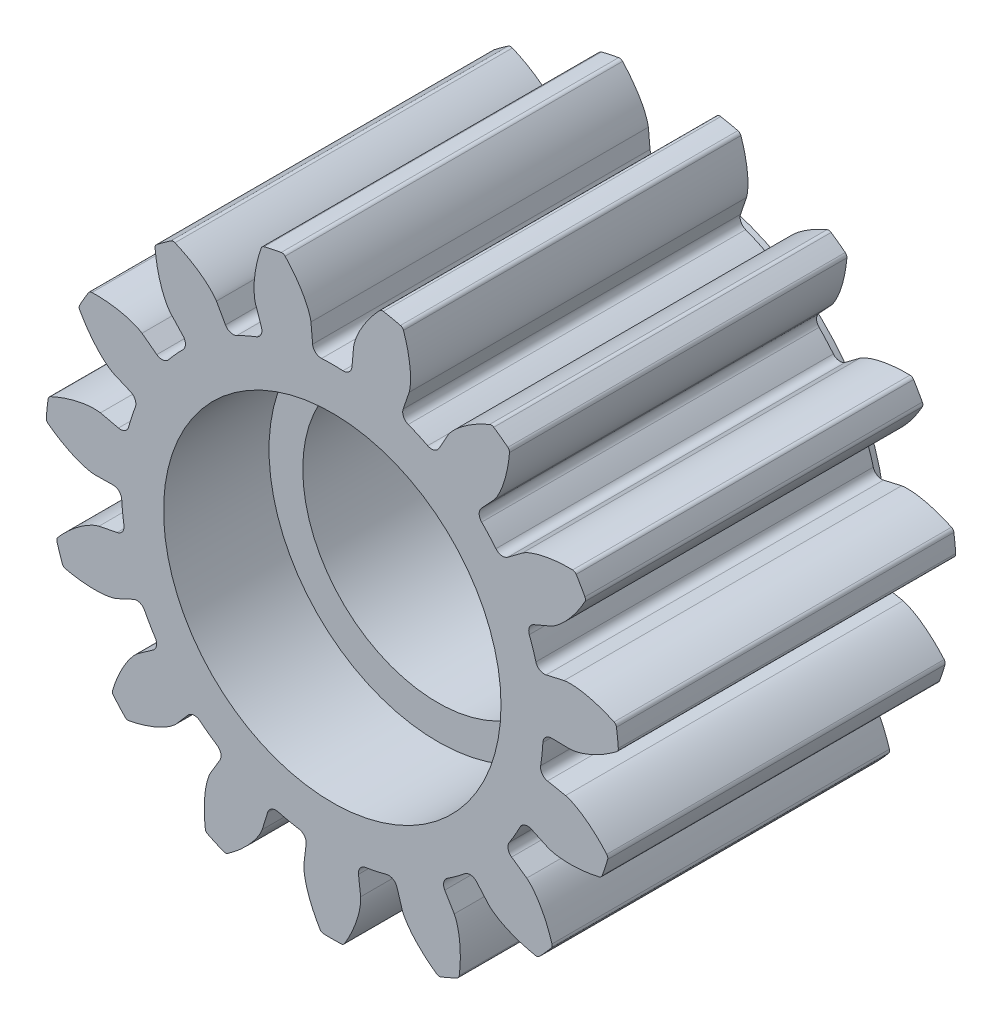
SolidWorks part; units mm, degrees
material "Alloy Steel"
ref_plane "Front" through (0, 0, 0) normal (0, 0, 1) x (1, 0, 0)
ref_plane "Top" through (0, 0, 0) normal (0, 1, 0) x (1, 0, 0)
ref_plane "Right" through (0, 0, 0) normal (1, 0, 0) x (0, 0, -1)
sketch "Sketch1" plane through (0, 0, 0) normal (0, 0, 1) x (1, 0, 0)
  circle A0 centre (0, 0) radius 10.795
  dimension "OutsideDiameter" = 21.59
extrude "Boss-Extrude1" add sketch "Sketch1" along normal blind 12.7
sketch "Sketch3" plane through (0, 0, 0) normal (0, 0, 1) x (1, 0, 0)
  line L0 (0, 0) -> (43.7181, 0) construction
  line L2 (0, 0) -> (-0.712, 7.9055) construction
  line L3 (0, 0) -> (0.712, 7.9055) construction
  line L4 (0.712, 7.9055) -> (0.8028, 8.9145) construction
  line L5 (0, 0) -> (0, 61.276) construction
  line L6 (-0.712, 7.9055) -> (-0.8028, 8.9145) construction
  circle A0 centre (0, 0) radius 10.795 construction
  circle A1 centre (0, 0) radius 9.525 construction
  circle A2 centre (0, 0) radius 8.9506 construction
  arc A3 (0.712, 7.9055) -> (-0.712, 7.9055) centre (0, 0) ccw construction
  arc A5 (1.8351, 10.6379) -> (-1.8351, 10.6379) centre (0, 0) ccw
  spline S0 degree 4 poles (-0.8028, 8.9145) (-0.8031, 8.9175) (-0.8041, 8.9259) (-0.8066, 8.9416) (-0.8113, 8.9673) (-0.8183, 8.9998) (-0.8287, 9.0417) (-0.8426, 9.0906) (-0.8594, 9.1441) (-0.8795, 9.2019) (-0.9011, 9.2592) (-0.9242, 9.316) (-0.9484, 9.3722) (-0.9793, 9.4398) (-1.0185, 9.5203) (-1.0674, 9.6134) (-1.1265, 9.7178) (-1.1905, 9.8228) (-1.2566, 9.925) (-1.327, 10.0269) (-1.3976, 10.1244) (-1.4745, 10.2242) (-1.5473, 10.3155) (-1.6328, 10.416) (-1.7029, 10.4966) (-1.7995, 10.6009) (-1.8578, 10.6619) (-1.9274, 10.7325) (-1.9591, 10.7635) (-1.9785, 10.7826) knots 0 0 0 0 0 0.005377 0.015084 0.028532 0.04661 0.064855 0.092111 0.119476 0.146842 0.174209 0.201575 0.228941 0.256307 0.307035 0.361767 0.4165 0.471232 0.525964 0.580697 0.635429 0.690161 0.744894 0.799626 0.854358 0.909091 0.954545 1 1 1 1 1 construction
  spline S1 degree 4 poles (-0.8028, 8.9145) (-0.8031, 8.9175) (-0.8041, 8.9259) (-0.8066, 8.9416) (-0.8113, 8.9673) (-0.8183, 8.9998) (-0.8287, 9.0417) (-0.8426, 9.0906) (-0.8594, 9.1441) (-0.8795, 9.2019) (-0.9011, 9.2592) (-0.9242, 9.316) (-0.9484, 9.3722) (-0.9793, 9.4398) (-1.0185, 9.5203) (-1.0674, 9.6134) (-1.1265, 9.7178) (-1.1905, 9.8228) (-1.2566, 9.925) (-1.327, 10.0269) (-1.3976, 10.1244) (-1.4745, 10.2242) (-1.5473, 10.3155) (-1.6328, 10.416) (-1.7029, 10.4966) (-1.7786, 10.5782) (-1.8159, 10.6178) (-1.8351, 10.6379) knots 0 0 0 0 0 0.005377 0.015084 0.028532 0.04661 0.064855 0.092111 0.119476 0.146842 0.174209 0.201575 0.228941 0.256307 0.307035 0.361767 0.4165 0.471232 0.525964 0.580697 0.635429 0.690161 0.744894 0.799626 0.854358 0.909091 0.909091 0.909091 0.909091 0.909091
  spline S2 degree 4 poles (0.8028, 8.9145) (0.8031, 8.9175) (0.8041, 8.9259) (0.8066, 8.9416) (0.8113, 8.9673) (0.8183, 8.9998) (0.8287, 9.0417) (0.8426, 9.0906) (0.8594, 9.1441) (0.8795, 9.2019) (0.9011, 9.2592) (0.9242, 9.316) (0.9484, 9.3722) (0.9793, 9.4398) (1.0185, 9.5203) (1.0674, 9.6134) (1.1265, 9.7178) (1.1905, 9.8228) (1.2566, 9.925) (1.327, 10.0269) (1.3976, 10.1244) (1.4745, 10.2242) (1.5473, 10.3155) (1.6328, 10.416) (1.7029, 10.4966) (1.7995, 10.6009) (1.8578, 10.6619) (1.9274, 10.7325) (1.9591, 10.7635) (1.9785, 10.7826) knots 0 0 0 0 0 0.005377 0.015084 0.028532 0.04661 0.064855 0.092111 0.119476 0.146842 0.174209 0.201575 0.228941 0.256307 0.307035 0.361767 0.4165 0.471232 0.525964 0.580697 0.635429 0.690161 0.744894 0.799626 0.854358 0.909091 0.954545 1 1 1 1 1 construction
  spline S3 degree 4 poles (0.8028, 8.9145) (0.8031, 8.9175) (0.8041, 8.9259) (0.8066, 8.9416) (0.8113, 8.9673) (0.8183, 8.9998) (0.8287, 9.0417) (0.8426, 9.0906) (0.8594, 9.1441) (0.8795, 9.2019) (0.9011, 9.2592) (0.9242, 9.316) (0.9484, 9.3722) (0.9793, 9.4398) (1.0185, 9.5203) (1.0674, 9.6134) (1.1265, 9.7178) (1.1905, 9.8228) (1.2566, 9.925) (1.327, 10.0269) (1.3976, 10.1244) (1.4745, 10.2242) (1.5473, 10.3155) (1.6328, 10.416) (1.7029, 10.4966) (1.7786, 10.5782) (1.8159, 10.6178) (1.8351, 10.6379) knots 0 0 0 0 0 0.005377 0.015084 0.028532 0.04661 0.064855 0.092111 0.119476 0.146842 0.174209 0.201575 0.228941 0.256307 0.307035 0.361767 0.4165 0.471232 0.525964 0.580697 0.635429 0.690161 0.744894 0.799626 0.854358 0.909091 0.909091 0.909091 0.909091 0.909091
  dimension "OutsideDiameter" = 21.59
  dimension "PitchCircle" = 19.05
  dimension "BaseCircle" = 17.9011
  dimension "DedendumCircle" = 15.875
sketch "DCLTBC" plane through (0, 0, 0) normal (0, 0, 1) x (1, 0, 0)
  line L0 (0, 0) -> (41.04, 0) construction
  line L1 (-0.712, 7.9055) -> (-0.8028, 8.9145) construction
  line L2 (0.712, 7.9055) -> (0.8028, 8.9145) construction
  line L3 (-0.7404, 8.2217) -> (-0.8028, 8.9145)
  line L4 (0.7404, 8.2217) -> (0.8028, 8.9145)
  line L5 (0, 0) -> (0, 104.9356) construction
  circle A0 centre (0, 0) radius 10.795
  circle A1 centre (0, 0) radius 9.525 construction
  circle A2 centre (0, 0) radius 8.9506 construction
  arc A3 (0.712, 7.9055) -> (-0.712, 7.9055) centre (0, 0) ccw construction
  arc A4 (0.4015, 7.9273) -> (-0.4015, 7.9273) centre (0, 0) ccw
  arc A5 (-0.7404, 8.2217) -> (-0.4015, 7.9273) centre (-0.4179, 8.2508) ccw
  arc A7 (0.7404, 8.2217) -> (0.4015, 7.9273) centre (0.4179, 8.2508) cw
  spline S0 degree 4 poles (-995.1793, -96.8983) (-12.295, 6.8209) (-0.9092, 8.2064) (-0.7443, 8.6021) (-0.8113, 8.9673) (-0.8183, 8.9998) (-0.8287, 9.0417) (-0.8426, 9.0906) (-0.8594, 9.1441) (-0.8795, 9.2019) (-0.9011, 9.2592) (-0.9242, 9.316) (-0.9484, 9.3722) (-0.9793, 9.4398) (-1.0185, 9.5203) (-1.0674, 9.6134) (-1.1265, 9.7178) (-1.1905, 9.8228) (-1.2566, 9.925) (-1.327, 10.0269) (-1.3976, 10.1244) (-1.4745, 10.2242) (-1.5473, 10.3155) (-1.6328, 10.416) (-2.006, 10.8448) (-3.4164, 12.2251) (15.2695, -7.4447) (-693.9148, 732.4306) knots -0.616876 -0.616876 -0.616876 -0.616876 -0.616876 0.005377 0.015084 0.028532 0.04661 0.064855 0.092111 0.119476 0.146842 0.174209 0.201575 0.228941 0.256307 0.307035 0.361767 0.4165 0.471232 0.525964 0.580697 0.635429 0.690161 0.744894 0.799626 0.854358 1.855242 1.855242 1.855242 1.855242 1.855242 only from (-0.8028, 8.9145) to (-1.8351, 10.6379) construction
  spline S1 degree 4 poles (995.1793, -96.8983) (12.295, 6.8209) (0.9092, 8.2064) (0.7443, 8.6021) (0.8113, 8.9673) (0.8183, 8.9998) (0.8287, 9.0417) (0.8426, 9.0906) (0.8594, 9.1441) (0.8795, 9.2019) (0.9011, 9.2592) (0.9242, 9.316) (0.9484, 9.3722) (0.9793, 9.4398) (1.0185, 9.5203) (1.0674, 9.6134) (1.1265, 9.7178) (1.1905, 9.8228) (1.2566, 9.925) (1.327, 10.0269) (1.3976, 10.1244) (1.4745, 10.2242) (1.5473, 10.3155) (1.6328, 10.416) (2.006, 10.8448) (3.4164, 12.2251) (-15.2695, -7.4447) (693.9148, 732.4306) knots -0.616876 -0.616876 -0.616876 -0.616876 -0.616876 0.005377 0.015084 0.028532 0.04661 0.064855 0.092111 0.119476 0.146842 0.174209 0.201575 0.228941 0.256307 0.307035 0.361767 0.4165 0.471232 0.525964 0.580697 0.635429 0.690161 0.744894 0.799626 0.854358 1.855242 1.855242 1.855242 1.855242 1.855242 only from (0.8028, 8.9145) to (1.8351, 10.6379) construction
  spline S2 degree 4 poles (-0.8028, 8.9145) (-0.8031, 8.9175) (-0.8041, 8.9259) (-0.8066, 8.9416) (-0.8113, 8.9673) (-0.8183, 8.9998) (-0.8287, 9.0417) (-0.8426, 9.0906) (-0.8594, 9.1441) (-0.8795, 9.2019) (-0.9011, 9.2592) (-0.9242, 9.316) (-0.9484, 9.3722) (-0.9793, 9.4398) (-1.0185, 9.5203) (-1.0674, 9.6134) (-1.1265, 9.7178) (-1.1905, 9.8228) (-1.2566, 9.925) (-1.327, 10.0269) (-1.3976, 10.1244) (-1.4745, 10.2242) (-1.5473, 10.3155) (-1.6328, 10.416) (-1.7029, 10.4966) (-1.7786, 10.5782) (-1.8159, 10.6178) (-1.8351, 10.6379) knots 0 0 0 0 0 0.005377 0.015084 0.028532 0.04661 0.064855 0.092111 0.119476 0.146842 0.174209 0.201575 0.228941 0.256307 0.307035 0.361767 0.4165 0.471232 0.525964 0.580697 0.635429 0.690161 0.744894 0.799626 0.854358 0.909091 0.909091 0.909091 0.909091 0.909091
  spline S3 degree 4 poles (0.8028, 8.9145) (0.8031, 8.9175) (0.8041, 8.9259) (0.8066, 8.9416) (0.8113, 8.9673) (0.8183, 8.9998) (0.8287, 9.0417) (0.8426, 9.0906) (0.8594, 9.1441) (0.8795, 9.2019) (0.9011, 9.2592) (0.9242, 9.316) (0.9484, 9.3722) (0.9793, 9.4398) (1.0185, 9.5203) (1.0674, 9.6134) (1.1265, 9.7178) (1.1905, 9.8228) (1.2566, 9.925) (1.327, 10.0269) (1.3976, 10.1244) (1.4745, 10.2242) (1.5473, 10.3155) (1.6328, 10.416) (1.7029, 10.4966) (1.7786, 10.5782) (1.8159, 10.6178) (1.8351, 10.6379) knots 0 0 0 0 0 0.005377 0.015084 0.028532 0.04661 0.064855 0.092111 0.119476 0.146842 0.174209 0.201575 0.228941 0.256307 0.307035 0.361767 0.4165 0.471232 0.525964 0.580697 0.635429 0.690161 0.744894 0.799626 0.854358 0.909091 0.909091 0.909091 0.909091 0.909091
  dimension "OutsideDiameter" = 21.59
  dimension "PitchCircle" = 19.05
  dimension "BaseCircle" = 17.9011
  dimension "D1" = 0.3238
extrude "Cut-Extrude-DCLTBC" cut sketch "DCLTBC" along normal through all contours L4 S3 A0 S2 L3 A5 A4 A7 region at (0, 9.5988, 0)
fillet "Fillet-DCLTBC" radius 0.1619 2 edges at (1.8351, 10.6379, 6.35) (-1.8351, 10.6379, 6.35)
pattern_circular "CirPattern-DCLTBC" count 15 over 360 about axis through (0, 0, 12.7) along (0, 0, 1) of "Cut-Extrude-DCLTBC", "Fillet-DCLTBC"
sketch "DCGTBC" [suppressed] plane through (0, 0, 0) normal (0, 0, 1) x (1, 0, 0)
  line L0 (0, 0) -> (41.04, 0) construction
  line L5 (0, 0) -> (0, 104.9356) construction
  circle A0 centre (0, 0) radius 33.02
  circle A1 centre (0, 0) radius 31.75 construction
  circle A2 centre (0, 0) radius 29.8352 construction
  arc A3 (0.498, 30.1584) -> (-0.498, 30.1584) centre (0, 0) ccw construction
  arc A5 (0.2614, 30.1614) -> (0.5806, 30.4159) centre (0.2642, 30.4852) ccw
  arc A7 (-0.5806, 30.4159) -> (-0.2614, 30.1614) centre (-0.2642, 30.4852) ccw
  arc A11 (0.2614, 30.1614) -> (-0.2614, 30.1614) centre (0, 0) ccw
  spline S2 degree 4 poles (-999.5536, -12.7278) (-12.5544, 28.0053) (-0.6553, 28.7383) (-0.4506, 29.3302) (-0.4983, 29.9192) (-0.504, 29.9738) (-0.5128, 30.0443) (-0.5251, 30.1273) (-0.5406, 30.2184) (-0.5595, 30.3176) (-0.5803, 30.4164) (-0.6028, 30.5149) (-0.6268, 30.6129) (-0.6577, 30.7316) (-0.6973, 30.8738) (-0.7475, 31.0397) (-0.8089, 31.2277) (-0.8762, 31.4191) (-0.9464, 31.6071) (-1.0218, 31.7967) (-1.098, 31.98) (-1.1818, 32.1701) (-1.2615, 32.3454) (-1.3559, 32.5413) (-1.7288, 33.2996) (-3.049, 35.6508) (11.5222, 8.1522) (-473.0995, 914.7978) knots -0.593942 -0.593942 -0.593942 -0.593942 -0.593942 0.005377 0.015084 0.028532 0.04661 0.064855 0.092111 0.119476 0.146842 0.174209 0.201575 0.228941 0.256307 0.307035 0.361767 0.4165 0.471232 0.525964 0.580697 0.635429 0.690161 0.744894 0.799626 0.854358 1.740449 1.740449 1.740449 1.740449 1.740449 only from (-0.4926, 29.8312) to (-1.5817, 32.9821) construction
  spline S3 degree 4 poles (999.5536, -12.7278) (12.5544, 28.0053) (0.6553, 28.7383) (0.4506, 29.3302) (0.4983, 29.9192) (0.504, 29.9738) (0.5128, 30.0443) (0.5251, 30.1273) (0.5406, 30.2184) (0.5595, 30.3176) (0.5803, 30.4164) (0.6028, 30.5149) (0.6268, 30.6129) (0.6577, 30.7316) (0.6973, 30.8738) (0.7475, 31.0397) (0.8089, 31.2277) (0.8762, 31.4191) (0.9464, 31.6071) (1.0218, 31.7967) (1.098, 31.98) (1.1818, 32.1701) (1.2615, 32.3454) (1.3559, 32.5413) (1.7288, 33.2996) (3.049, 35.6508) (-11.5222, 8.1522) (473.0995, 914.7978) knots -0.593942 -0.593942 -0.593942 -0.593942 -0.593942 0.005377 0.015084 0.028532 0.04661 0.064855 0.092111 0.119476 0.146842 0.174209 0.201575 0.228941 0.256307 0.307035 0.361767 0.4165 0.471232 0.525964 0.580697 0.635429 0.690161 0.744894 0.799626 0.854358 1.740449 1.740449 1.740449 1.740449 1.740449 only from (0.4926, 29.8312) to (1.5817, 32.9821) construction
  spline S4 degree 4 poles (-0.5806, 30.4159) (-0.5833, 30.4283) (-0.5915, 30.4654) (-0.6058, 30.527) (-0.6268, 30.6129) (-0.6577, 30.7316) (-0.6973, 30.8738) (-0.7475, 31.0397) (-0.8089, 31.2277) (-0.8762, 31.4191) (-0.9464, 31.6071) (-1.0218, 31.7967) (-1.098, 31.98) (-1.1818, 32.1701) (-1.2615, 32.3454) (-1.3559, 32.5413) (-1.4337, 32.6994) (-1.5183, 32.8623) (-1.5601, 32.9416) (-1.5817, 32.9821) knots 0.160405 0.160405 0.160405 0.160405 0.160405 0.174209 0.201575 0.228941 0.256307 0.307035 0.361767 0.4165 0.471232 0.525964 0.580697 0.635429 0.690161 0.744894 0.799626 0.854358 0.909091 0.909091 0.909091 0.909091 0.909091
  spline S5 degree 4 poles (0.5806, 30.4159) (0.5833, 30.4283) (0.5915, 30.4654) (0.6058, 30.527) (0.6268, 30.6129) (0.6577, 30.7316) (0.6973, 30.8738) (0.7475, 31.0397) (0.8089, 31.2277) (0.8762, 31.4191) (0.9464, 31.6071) (1.0218, 31.7967) (1.098, 31.98) (1.1818, 32.1701) (1.2615, 32.3454) (1.3559, 32.5413) (1.4337, 32.6994) (1.5183, 32.8623) (1.5601, 32.9416) (1.5817, 32.9821) knots 0.160405 0.160405 0.160405 0.160405 0.160405 0.174209 0.201575 0.228941 0.256307 0.307035 0.361767 0.4165 0.471232 0.525964 0.580697 0.635429 0.690161 0.744894 0.799626 0.854358 0.909091 0.909091 0.909091 0.909091 0.909091
  dimension "OutsideDiameter" = 21.59
  dimension "PitchCircle" = 19.05
  dimension "BaseCircle" = 17.9011
  dimension "D1" = 0.3238
extrude "Cut-Extrude-DCGTBC" [suppressed] cut sketch "DCGTBC" along normal through all contours A5 S5 A0 S4 A7 A11
fillet "Fillet-DCGTBC" [suppressed] radius 0.1619
pattern_circular "CirPattern-DCGTBC" [suppressed] count 15 over 360 of bodies 112
sketch "Sketch4" plane through (0, 0, 12.7) normal (0, 0, 1) x (1, 0, 0)
  circle A0 centre (0, 0) radius 4.7625
  dimension "D1" = 9.525
extrude "Cut-Extrude2" cut sketch "Sketch4" against normal through all
sketch "Sketch5" plane through (0, 0, 12.7) normal (0, 0, 1) x (1, 0, 0)
  circle A0 centre (0, 0) radius 6.35
  dimension "D1" = 12.7
extrude "Cut-Extrude3" cut sketch "Sketch5" against normal blind 3.9688
sketch "Sketch6" plane through (0, 0, 8.7312) normal (0, 0, 1) x (1, 0, 0)
  circle A0 centre (0, 0) radius 5.08
  dimension "D1" = 10.16
extrude "Cut-Extrude4" cut sketch "Sketch6" against normal through all
sketch "Sketch7" plane through (0, 0, 0) normal (0, 0, -1) x (-1, 0, 0)
  circle A0 centre (0, 0) radius 5.08 construction
  circle A1 centre (0, 0) radius 5.08
  circle A2 centre (0, 0) radius 7.874
  dimension "D1" = 15.748
extrude "Boss-Extrude2" add sketch "Sketch7" along normal blind 0.254
equation "\"DiametralPitch\"= 20'Diametral Pitch"
equation "\"NumTeeth\"= 15'Number of Teeth"
equation "\"PressureAngle\"= 20deg'Pressure Angle"
equation "\"Addendum\"= 1 / \"DiametralPitch\"'Addendum"
equation "\"Dedendum\"= 1.25 / \"DiametralPitch\"'Dedendum"
equation "\"WorkingDepth\"= 2 / \"DiametralPitch\"'Working Depth - here for REF (Not used in building model)"
equation "\"WholeDepth\"= 2.25 / \"DiametralPitch\"'Whole Depth - here for REF (Not used in building model)"
equation "\"Clearance\"= .19 / \"DiametralPitch\"'Clearance"
equation "\"CircularPitch\"= pi / \"DiametralPitch\"'Circular Pitch - here for REF (Not used in building model)"
equation "\"PitchCircle\"= \"NumTeeth\" / \"DiametralPitch\"'Pitch Circle - or - Pitch Diameter"
equation "\"OutsideDiameter\"= ( \"NumTeeth\" + 2 ) / \"DiametralPitch\"'Outside Diameter"
equation "\"Fillet\"= \"Clearance\" * cos ( \"PressureAngle\" ) * tan ( ( 90 + \"PressureAngle\" ) / 2 )'Fillet"
equation "\"AddendumCircle\"= \"PitchCircle\" + ( 2 * \"Addendum\" )'Addendum Circle - or - Addendum Diameter"
equation "\"DedendumCircle\"= \"PitchCircle\" - ( 2 * \"Dedendum\" )'Dedendum Circle - or - Dedendum Diameter"
equation "\"BaseCircle\"= \"PitchCircle\" * cos ( \"PressureAngle\" )'Base Circle - Base Diameter"
equation "\"PitchAngle\"= 360deg / \"NumTeeth\"'Pitch Angle"
equation "\"Alpha\"= sqr ( \"PitchCircle\" ^ 2 - \"BaseCircle\" ^ 2 ) / \"BaseCircle\" * 180 / PI - \"PressureAngle\"'Alpha - Used for Calculating Beta"
equation "\"Beta\"= ( \"PitchAngle\" / 4 - ( \"Alpha\" - 90 ) )'Beta - Used in definition of the parameters for the parametric equation driven curve"
equation "\"Gamma\"= ( \"PitchAngle\" / 4 - ( \"Alpha\" + 90 ) )'Gamma - Used in definition of the parameters for the parametric equation driven curve"
equation "\"Phi\"= sqr ( ( \"AddendumCircle\" / 2 ) ^ 2 - ( \"BaseCircle\" / 2 ) ^ 2 ) / ( \"BaseCircle\" / 2 )'Phi - Used in definition of the parameters for the parametric equation driven curve"
equation "\"DCGTBC\"= iif ( ( \"DedendumCircle\" + ( \"Fillet\" * 2 ) ) > \"BaseCircle\" , \"unsuppressed\" , \"suppressed\" )'if Dedendum Circle +2X Fillet IS GREATER THAN BaseCircle THEN Unsuppress OR Suppress FEATURE"
equation "\"DCLTBC\"= iif ( ( \"DedendumCircle\" + ( \"Fillet\" * 2 ) ) > \"BaseCircle\" , \"suppressed\" , \"unsuppressed\" )'if Dedendum Circle +2X Fillet IS GREATER THAN BaseCircle THEN Suppress OR Unsuppress FEATURE"
equation "\"Cut-Extrude-DCGTBC\"= iif ( ( \"DedendumCircle\" + ( \"Fillet\" * 2 ) ) > \"BaseCircle\" , \"unsuppressed\" , \"suppressed\" )'if Dedendum Circle +2X Fillet IS GREATER THAN BaseCircle THEN UnsuppressORSuppress FEATURE"
equation "\"Cut-Extrude-DCLTBC\"= iif ( ( \"DedendumCircle\" + ( \"Fillet\" * 2 ) ) > \"BaseCircle\" , \"suppressed\" , \"unsuppressed\" )'if Dedendum Circle +2X Fillet IS GREATER THAN BaseCircle THEN SuppressORUnsuppress FEATURE"
equation "\"CirPattern-DCGTBC\"= iif ( ( \"DedendumCircle\" + ( \"Fillet\" * 2 ) ) > \"BaseCircle\" , \"unsuppressed\" , \"suppressed\" )'if Dedendum Circle +2X Fillet IS GREATER THAN \"BaseCircle\" THEN UnsuppressORSuppress FEATURE"
equation "\"CirPattern-DCLTBC\"= iif ( ( \"DedendumCircle\" + ( \"Fillet\" * 2 ) ) > \"BaseCircle\" , \"suppressed\" , \"unsuppressed\" )'if Dedendum Circle +2X Fillet IS GREATER THAN \"BaseCircle\" THEN SuppressORUnsuppress FEATURE"
equation "\"Fillet-DCGTBC\"= iif ( ( \"DedendumCircle\" + ( \"Fillet\" * 2 ) ) > \"BaseCircle\" , \"unsuppressed\" , \"suppressed\" )'if Dedendum Circle +2X Fillet IS GREATER THAN \"BaseCircle\" THEN UnsuppressORSuppress FEATURE"
equation "\"Fillet-DCLTBC\"= iif ( ( \"DedendumCircle\" + ( \"Fillet\" * 2 ) ) > \"BaseCircle\" , \"suppressed\" , \"unsuppressed\" )'if Dedendum Circle +2X Fillet IS GREATER THAN \"BaseCircle\" THEN SuppressORUnsuppress FEATURE"
equation "\"D1@CirPattern-DCGTBC\"=\"NumTeeth\""
equation "\"D1@CirPattern-DCLTBC\"=\"NumTeeth\""
equation "\"D1@DCGTBC\"=\"Fillet\""
equation "\"D1@DCLTBC\"=\"Fillet\""
equation "\"D1@Fillet-DCLTBC\"=\"Fillet\"/2"
equation "\"D1@Fillet-DCGTBC\"=\"Fillet\"/2"
